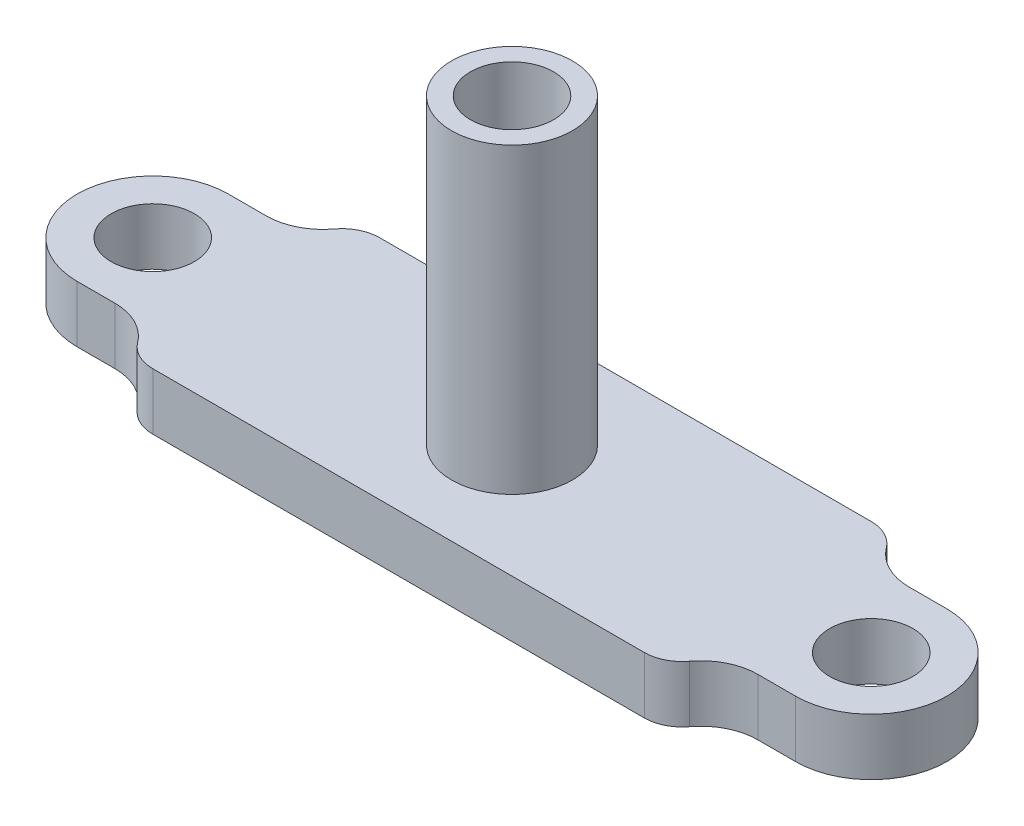
SolidWorks part; units mm, degrees
ref_plane "Front Plane" through (0, 0, 0) normal (0, 0, 1) x (1, 0, 0)
ref_plane "Top Plane" through (0, 0, 0) normal (0, 1, 0) x (1, 0, 0)
ref_plane "Right Plane" through (0, 0, 0) normal (1, 0, 0) x (0, 0, -1)
sketch "Sketch1" plane through (0, 0, 0) normal (0, 1, 0) x (1, 0, 0)
  line L0 (-9.5, 2) -> (-7.5, 2)
  line L1 (-7.5, 3) -> (7.5, 3)
  line L2 (-7.5, 3) -> (-7.5, 2)
  line L3 (-7.5, -3) -> (7.5, -3)
  line L4 (7.5, 3) -> (7.5, 2)
  line L5 (-9.5, -2) -> (-7.5, -2)
  line L6 (-7.5, -2) -> (-7.5, -3)
  line L7 (0, 1.476) -> (0, -0.5732) construction
  line L8 (9.5, -2) -> (7.5, -2)
  line L9 (9.5, 2) -> (7.5, 2)
  line L10 (7.5, -2) -> (7.5, -3)
  circle A0 centre (-9.5, 0) radius 1.1
  arc A1 (-9.5, 2) -> (-9.5, -2) centre (-9.5, 0) ccw
  circle A2 centre (9.5, 0) radius 1.1
  arc A3 (9.5, 2) -> (9.5, -2) centre (9.5, 0) cw
  point P9 (0, 3)
  dimension "D1" = 2.2
  dimension "D2" = 4
  dimension "D3" = 6
  dimension "D4" = 15
  dimension "D5" = 3
extrude "Boss-Extrude1" add sketch "Sketch1" along normal blind 1.5
fillet "Fillet1" radius 1 4 edges at (7.5, 0.75, 3) (7.5, 0.75, -3) (-7.5, 0.75, -3) (-7.5, 0.75, 3)
fillet "Fillet2" radius 1.5 4 edges at (7.5, 0.75, 2) (7.5, 0.75, -2) (-7.5, 0.75, -2) (-7.5, 0.75, 2)
sketch "Sketch2" plane through (0, 1.5, 0) normal (0, 1, 0) x (1, 0, 0)
  circle A0 centre (0, 0) radius 1.1
  circle A1 centre (0, 0) radius 1.6
  dimension "D1" = 2.2
  dimension "D2" = 3.2
extrude "Boss-Extrude2" add sketch "Sketch2" along normal blind 8
